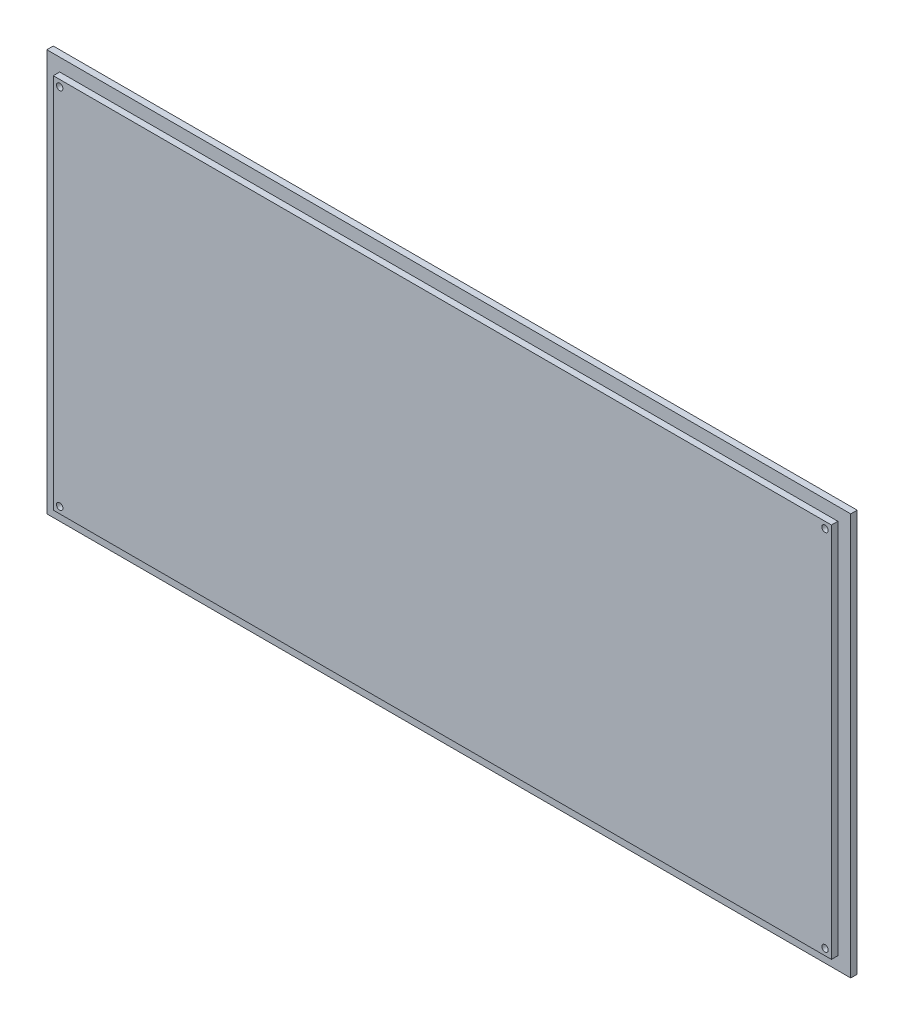
SolidWorks part; units mm, degrees
ref_plane "Ebene vorne" through (0, 0, 0) normal (0, 0, 1) x (1, 0, 0)
ref_plane "Ebene oben" through (0, 0, 0) normal (0, 1, 0) x (1, 0, 0)
ref_plane "Ebene rechts" through (0, 0, 0) normal (1, 0, 0) x (0, 0, -1)
sketch "Skizze1" plane through (0, 0, 0) normal (0, 0, 1) x (1, 0, 0)
  line L1 (0, 125) -> (250, 125)
  line L2 (0, 125) -> (0, 0)
  line L3 (0, 0) -> (250, 0)
  line L4 (250, 125) -> (250, 0)
  dimension "D1" = 250
  dimension "D2" = 125
extrude "Aufsatz-Linear austragen1" add sketch "Skizze1" along normal blind 2 contours L2 L1 L4 L3
sketch "Skizze2" plane through (0, 0, 2) normal (0, 0, 1) x (1, 0, 0)
  line L0 (0, 125) -> (0, 0) construction
  line L1 (4, 121) -> (246, 121)
  line L2 (4, 121) -> (4, 4)
  line L3 (4, 4) -> (246, 4)
  line L4 (246, 121) -> (246, 4)
  line L5 (0, 125) -> (250, 125) construction
  line L6 (0, 0) -> (250, 0) construction
  line L7 (250, 125) -> (250, 0) construction
  dimension "D1" = 4
  dimension "D2" = 4
  dimension "D3" = 4
  dimension "D4" = 4
extrude "Aufsatz-Linear austragen2" add sketch "Skizze2" along normal blind 2
sketch "Skizze3" plane through (0, 0, 4) normal (0, 0, 1) x (1, 0, 0)
  line L0 (246, 121) -> (4, 121) construction
  line L1 (4, 121) -> (4, 4) construction
  line L2 (4, 121) -> (4, 4) construction
  line L3 (4, 4) -> (246, 4) construction
  line L4 (246, 4) -> (246, 121) construction
  line L5 (246, 121) -> (4, 121) construction
  circle A0 centre (6, 119) radius 1
  circle A1 centre (6, 6) radius 1
  circle A2 centre (244, 6) radius 1
  circle A3 centre (244, 119) radius 1
  point P2 (0, 0)
  point P19 (0, 0)
  point P20 (0, 0)
  point P21 (244.3338, 6.8214)
  point P26 (244.3831, 118.6333)
  point P27 (246, 118.7717)
  dimension "D1" = 2
  dimension "D3" = 2
  dimension "D5" = 2
  dimension "D2" = 2
  dimension "D4" = 2
  dimension "D6" = 2
  dimension "D7" = 2
  dimension "D8" = 2
extrude "Schnitt-Linear austragen1" cut sketch "Skizze3" against normal blind 32
